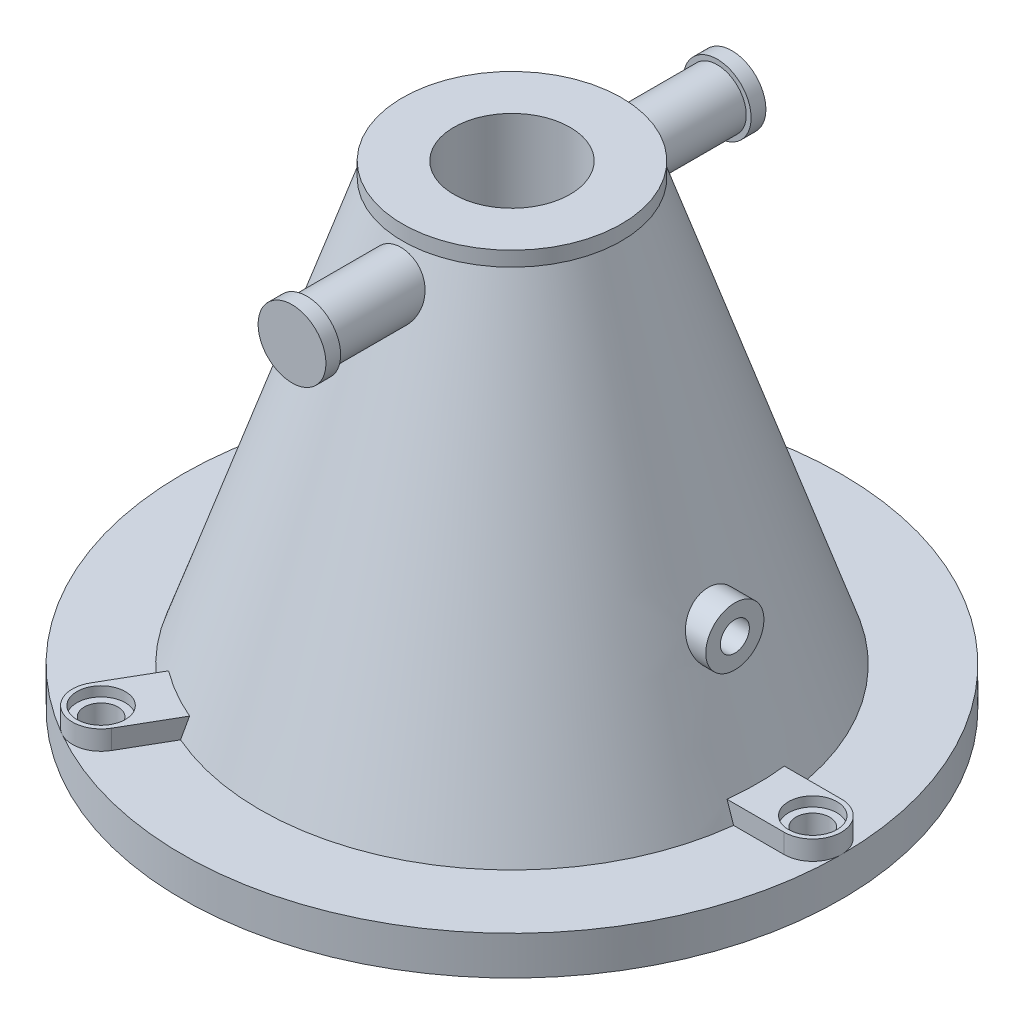
SolidWorks part; units mm, degrees
material "Plain Carbon Steel"
ref_plane "Front Plane" through (0, 0, 0) normal (0, 0, 1) x (1, 0, 0)
ref_plane "Top Plane" through (0, 0, 0) normal (0, 1, 0) x (1, 0, 0)
ref_plane "Right Plane" through (0, 0, 0) normal (1, 0, 0) x (0, 0, -1)
sketch "Sketch1" plane through (0, 0, 0) normal (0, 0, 1) x (1, 0, 0)
  line L0 (0, -0.4424) -> (0, 10.1782) construction
  line L1 (8.5, 0) -> (8.5, 1)
  line L5 (1.5, 12.25) -> (1.5, 3.25)
  line L6 (8.5, 0) -> (6.1731, 0)
  line L7 (6.1731, 0) -> (3.3485, 8.3545)
  line L8 (1.5, 3.25) -> (2.25, 3.25)
  line L9 (2.25, 3.25) -> (2.375, 8.207)
  line L10 (2.825, 11.87) -> (2.825, 12.25)
  line L11 (2.825, 12.25) -> (1.5, 12.25)
  line L12 (2.825, 11.87) -> (6.5, 1)
  line L13 (6.5, 1) -> (8.5, 1)
  arc A0 (2.375, 8.207) -> (3.3485, 8.3545) centre (2.8748, 8.1944) cw
  dimension "D2" = 0.38
  dimension "D7" = 0.5
  dimension "D1" = 8.5
  dimension "D4" = 6.5
  dimension "D5" = 1
  dimension "D6" = 2.25
  dimension "D8" = 0.63
  dimension "D9" = 1.5
  dimension "D10" = 2.375
  dimension "D11" = 3.25
  dimension "D12" = 12.25
  dimension "D13" = 2.825
revolve "Revolve1" add sketch "Sketch1" angle 360 about L0
sketch "Sketch5" plane through (0, 0, 0) normal (0, 0, 1) x (1, 0, 0)
  line L0 (4.13, 4.5) -> (5.75, 4.5)
  line L1 (-8.5, 0) -> (8.5, 0) construction
  dimension "D1" = 1.62
  dimension "D2" = 4.5
  dimension "D3" = 5.75
sweep "Sweep1" add path "Sketch5" circular profile diameter 1.5 parameters "D3"=1.5
sweep "Cut-Sweep1" cut path "Sketch5<2>" circular profile diameter 0.75 parameters "D3"=0.75
sketch "Sketch5<2>" plane through (0, 0, 0) normal (0, 0, 1) x (1, 0, 0) same geometry as "Sketch5"
sketch "Sketch16" plane through (0, 0, 0) normal (1, 0, 0) x (0, 0, -1)
  line L0 (2.375, 11) -> (5.675, 11)
  line L1 (0, 0) -> (0, -1.5071) construction
  line L3 (2.825, 12.25) -> (-2.825, 12.25) construction
  dimension "D1" = 5.675
  dimension "D2" = 2.375
  dimension "D3" = 1.25
sweep "Sweep5" add path "Sketch16" circular profile diameter 1.5 parameters "D3"=1.5
sketch "Sketch42" plane through (0, 0, -5.675) normal (0, 0, -1) x (-1, 0, 0)
  circle A0 centre (0, 11) radius 0.875
  dimension "D1" = 1.75
extrude "Boss-Extrude1" add sketch "Sketch42" against normal blind 0.38
mirror "Mirror2" about plane through (0, 0, 0) normal (0, 0, 1) of "Boss-Extrude1", "Sweep5"
sketch "Sketch44" plane through (0, 0, 0) normal (0, 1, 0) x (1, 0, 0)
  line L0 (7.76, 0.74) -> (6.26, 0.74)
  line L1 (7.76, -0.74) -> (6.26, -0.74)
  line L2 (6.26, 0.74) -> (6.26, -0.74)
  line L3 (-3.2391, -7.0904) -> (-2.4891, -5.7913)
  line L4 (-2.4891, -5.7913) -> (-3.7709, -5.0513)
  line L5 (-4.5209, -6.3504) -> (-3.7709, -5.0513)
  line L6 (-4.5209, 6.3504) -> (-3.7709, 5.0513)
  line L7 (-3.7709, 5.0513) -> (-2.4891, 5.7913)
  line L8 (-3.2391, 7.0904) -> (-2.4891, 5.7913)
  line L9 (-3.88, -6.7204) -> (0, 0) construction
  line L10 (0, 0) -> (7.76, 0) construction
  arc A0 (7.76, -0.74) -> (7.76, 0.74) centre (7.76, 0) ccw
  arc A1 (-4.5209, -6.3504) -> (-3.2391, -7.0904) centre (-3.88, -6.7204) ccw
  arc A2 (-3.2391, 7.0904) -> (-4.5209, 6.3504) centre (-3.88, 6.7204) ccw
  circle A4 centre (0, 0) radius 7.76 construction
  point P18 (0, 0)
  dimension "D1" = 0.74
  dimension "D6" = 15.52
  dimension "D3" = 1.5
  dimension "D5" = 120
  dimension "D4" = 3
extrude "Boss-Extrude2" add sketch "Sketch44" along normal blind 0.5 from offset 1
sketch "Sketch45" plane through (0, 0, 0) normal (0, 1, 0) x (1, 0, 0)
  circle A0 centre (7.76, 0) radius 0.625
  dimension "D1" = 1.25
extrude "Cut-Extrude1" cut sketch "Sketch45" against normal blind 0.25 from surface starting at face at (7.2196, 1.5, 0)
sketch "Sketch47" plane through (0, 0, 0) normal (0, 1, 0) x (1, 0, 0)
  circle A0 centre (7.76, 0) radius 0.435
  dimension "D1" = 0.87
extrude "Cut-Extrude3" cut sketch "Sketch47" against normal through all and the other way through all
pattern_circular "CirPattern1" count 3 over 360 about axis through (0, 12.25, 0) along (0, -1, 0) of "Cut-Extrude1", "Cut-Extrude3"
